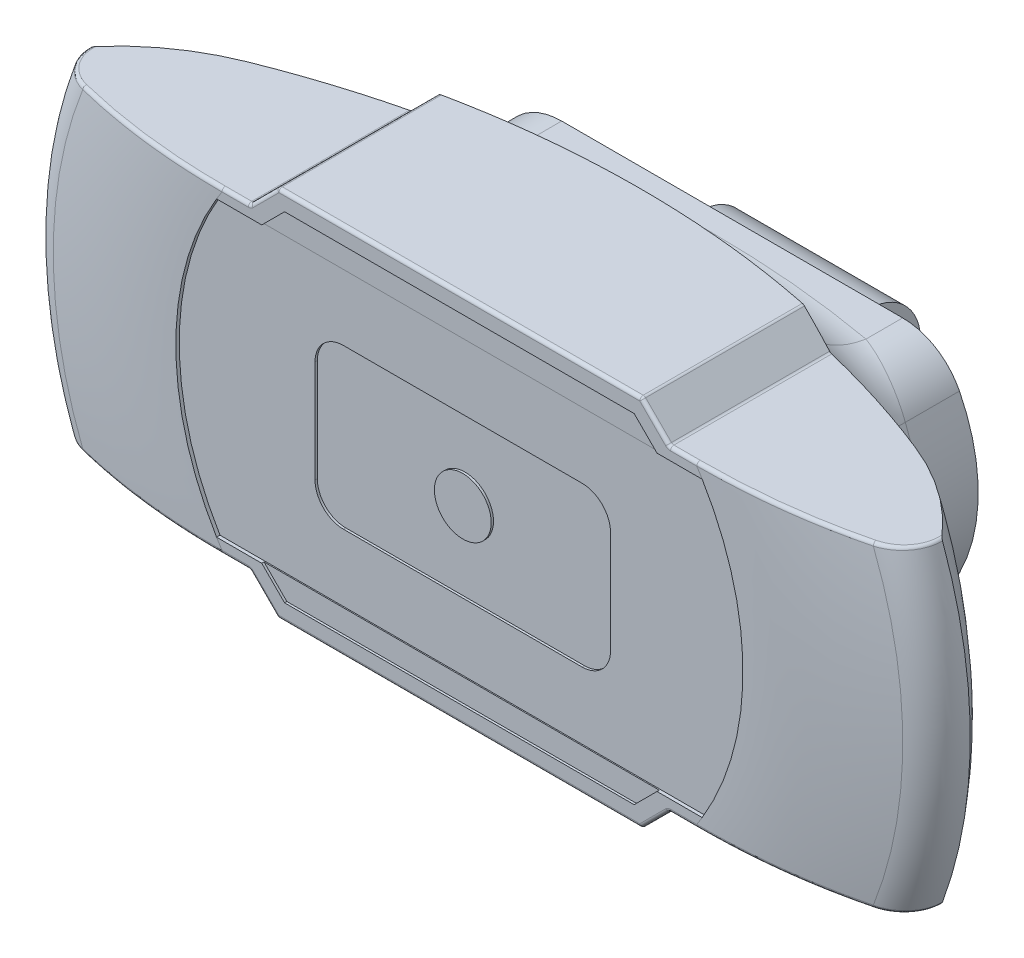
SolidWorks part; units mm, degrees
ref_plane "Front Plane" through (0, 0, 0) normal (0, 0, 1) x (1, 0, 0)
ref_plane "Top Plane" through (0, 0, 0) normal (0, 1, 0) x (1, 0, 0)
ref_plane "Right Plane" through (0, 0, 0) normal (1, 0, 0) x (0, 0, -1)
sketch "Sketch1" plane through (0, 0, 0) normal (0, 0, 1) x (1, 0, 0)
  line L0 (0, 16.4) -> (0, -16.4)
  line L1 (0, 16.4) -> (16, 16.4)
  line L2 (16, 16.4) -> (18.45, 13.95)
  line L3 (18.45, 13.95) -> (37.4353, 13.95)
  line L4 (0, -16.4) -> (16, -16.4)
  line L5 (16, -16.4) -> (18.45, -13.95)
  line L6 (18.45, -13.95) -> (37.4353, -13.95)
  line L7 (18.45, 13.95) -> (18.45, -13.95) construction
  line L8 (16, 16.4) -> (16, -16.4) construction
  arc A0 (37.4353, -13.95) -> (37.4353, 13.95) centre (0, 0) ccw
  dimension "D1" = 39.95
  dimension "D2" = 32.8
  dimension "D3" = 27.9
  dimension "D4" = 16
sketch "Sketch2" plane through (0, 0, 0) normal (0, 1, 0) x (1, 0, 0)
  line L0 (0, 0) -> (0, 17.6)
  line L1 (0, 17.6) -> (-9.2916, 17.6) construction
  line L2 (18.45, 0) -> (37.4353, 0) construction
  line L3 (39.95, 5) -> (39.95, 0) construction
  line L5 (24.95, 0) -> (0, 0)
  line L7 (0, 0) -> (39.95, 0) construction
  line L8 (37.4353, 0) -> (39.95, 0) construction
  line L9 (24.95, 0) -> (39.95, 5) construction
  arc A0 (0, 17.6) -> (32.5528, 10.7251) centre (0, -62.9071) cw
  arc A1 (32.5528, 10.7251) -> (39.95, 5) centre (24.6742, -7.0958) cw
  arc A3 (24.95, 0) -> (37.3743, 1.6406) centre (24.95, 47.8661) ccw
  arc A4 (37.3743, 1.6406) -> (39.95, 5) centre (36.4713, 5) ccw
  dimension "D1" = 17.6
  dimension "D2" = 15
  dimension "D3" = 5
revolve "Revolve1" add sketch "Sketch2" angle 180 mid plane about L0
sketch "Sketch3" plane through (0, 0, 0) normal (0, 0, 1) x (1, 0, 0)
  line L0 (0, 16.4) -> (0, -16.4) construction
  line L1 (0, -16.4) -> (16, -16.4) construction
  line L2 (16, -16.4) -> (18.45, -13.95) construction
  line L3 (18.45, -13.95) -> (37.4353, -13.95) construction
  line L4 (18.45, 13.95) -> (37.4353, 13.95) construction
  line L5 (16, 16.4) -> (18.45, 13.95) construction
  line L6 (0, 16.4) -> (16, 16.4) construction
  line L7 (0, 16.4) -> (0, -16.4)
  line L8 (0, -16.4) -> (16, -16.4)
  line L9 (16, -16.4) -> (18.45, -13.95)
  line L10 (18.45, -13.95) -> (37.4353, -13.95)
  line L11 (18.45, 13.95) -> (37.4353, 13.95)
  line L12 (16, 16.4) -> (18.45, 13.95)
  line L13 (0, 16.4) -> (16, 16.4)
  line L14 (-30, 46.4) -> (28.4264, 46.4)
  line L15 (28.4264, 46.4) -> (30.8764, 43.95)
  line L16 (30.8764, 43.95) -> (54.4187, 43.95)
  line L17 (30.8764, -43.95) -> (54.4187, -43.95)
  line L18 (28.4264, -46.4) -> (30.8764, -43.95)
  line L19 (-30, -46.4) -> (28.4264, -46.4)
  line L20 (-30, 46.4) -> (-30, -46.4)
  arc A0 (37.4353, -13.95) -> (37.4353, 13.95) centre (0, 0) ccw construction
  arc A1 (37.4353, -13.95) -> (37.4353, 13.95) centre (0, 0) ccw
  arc A2 (54.4187, -43.95) -> (54.4187, 43.95) centre (0, 0) ccw
  dimension "D1" = 30
extrude "Cut-Extrude1" cut sketch "Sketch3" against normal through all
mirror "Mirror1"
ref_plane "Plane1" through (0, 0, -24) normal (0, 0, 1) x (1, 0, 0)
sketch "Sketch4" plane through (0, 0, -24) normal (0, 0, 1) x (1, 0, 0)
  line L0 (0, 10) -> (0, -10) construction
  line L1 (-21.65, 0) -> (21.65, 0) construction
  line L2 (0, -10.6658) -> (0, 10.6658) construction
  line L3 (15, -10) -> (-15, -10)
  line L4 (15, -10) -> (15, 10) construction
  line L5 (15, 10) -> (-15, 10)
  line L6 (-15, -10) -> (-15, 10) construction
  line L7 (15, -10) -> (-15, 10) construction
  line L8 (15, 10) -> (-15, -10) construction
  line L9 (20, 6.9243) -> (20, -6.9243) construction
  arc A0 (20, 6.9243) -> (20, -6.9243) centre (6.2957, 0) cw
  arc A1 (15, 10) -> (20, 6.9243) centre (15, 4.398) cw
  arc A2 (15, -10) -> (20, -6.9243) centre (15, -4.398) ccw
  arc A3 (-15, -10) -> (-20, -6.9243) centre (-15, -4.398) cw
  arc A4 (-20, 6.9243) -> (-20, -6.9243) centre (-6.2957, 0) ccw
  arc A5 (-15, 10) -> (-20, 6.9243) centre (-15, 4.398) ccw
  point P4 (0, 0)
  dimension "D1" = 43.3
  dimension "D2" = 20
  dimension "D3" = 30
  dimension "D5" = 5
extrude "Boss-Extrude1" add sketch "Sketch4" along normal up to next
fillet "Fillet1" radius 6 8 edges at (-17.372, -9.4731, -15.1305) (-21.5174, 2.0133, -14.6451) (-18.5318, 8.7464, -14.9483) (0, 10, -16.9765) (17.372, 9.4731, -15.1305) (21.5174, -2.0133, -14.6451) (18.5318, -8.7464, -14.9483) (0, -10, -16.9765)
surface "Surface-Offset1" parameters "D1"=0.2
sketch "Sketch6" plane through (0, 0, 0) normal (0, 0, 1) x (1, 0, 0)
  line L21 (-17.3893, 12.8893) -> (-21.3628, 12.8893)
  line L23 (-24.95, 0) -> (0, 0)
  line L24 (-15.3787, 14.9) -> (-17.3893, 12.8893)
  line L25 (15.3787, 14.9) -> (-15.3787, 14.9)
  line L26 (17.3893, 12.8893) -> (15.3787, 14.9)
  line L27 (-15.3787, 14.9) -> (-17.3893, 12.8893)
  line L28 (15.3787, 14.9) -> (-15.3787, 14.9)
  line L29 (17.3893, 12.8893) -> (15.3787, 14.9)
  line L30 (0, 0) -> (24.95, 0)
  line L32 (21.3628, 12.8893) -> (17.3893, 12.8893)
  arc A2 (20.6857, -13.95) -> (20.6857, 13.95) centre (0, 0) ccw construction
  arc A3 (-20.6857, 13.95) -> (-20.6857, -13.95) centre (0, 0) ccw construction
  arc A4 (24.95, 0) -> (21.3628, 12.8893) centre (0, 0) ccw
  arc A5 (-21.3628, 12.8893) -> (-24.95, 0) centre (0, 0) ccw
  dimension "D1" = 1.5
extrude "Cut-Extrude6" cut sketch "Sketch6" against normal blind 0.3
mirror "Mirror2" of "Cut-Extrude6"
sketch "Sketch5" plane through (0, 0, -0.2) normal (0, 0, 1) x (1, 0, 0)
  line L1 (13, -7) -> (-13, -7)
  line L2 (13, -7) -> (13, 7)
  line L3 (13, 7) -> (-13, 7)
  line L4 (-13, -7) -> (-13, 7)
  line L5 (13, -7) -> (-13, 7) construction
  line L6 (13, 7) -> (-13, -7) construction
  circle A0 centre (0, 0) radius 2.5
  point P0 (0, 0)
  dimension "D3" = 5
  dimension "D1" = 26
  dimension "D2" = 14
extrude "Cut-Extrude2" cut sketch "Sketch5" against normal blind 0.3
fillet "Fillet2" radius 2.5 4 edges at (-13, 7, -0.4) (-13, -7, -0.4) (13, -7, -0.4) (13, 7, -0.4)
fillet "Fillet4" radius 0.3 8 edges at (18.45, 13.95, -7.1029) (16, -16.4, -7.1354) (18.45, -13.95, -7.1029) (16, 16.4, -7.1354) (-18.45, -13.95, -7.1029) (-16, -16.4, -7.1354) (-18.45, 13.95, -7.1029) (-16, 16.4, -7.1354)
fillet "Fillet5" radius 0.3 28 edges at (-19.63, -13.95, 0) (-17.225, -15.175, 0) (0, -16.4, 0) (17.225, -15.175, 0) (19.63, -13.95, 0) (15.9905, -16.3772, 0) (-15.9905, -16.3772, 0) (17.225, 15.175, 0) (0, 16.4, 0) (-17.225, 15.175, 0) (-15.9905, 16.3772, 0) (15.9905, 16.3772, 0) (-18.4595, -13.9728, 0) (18.4595, -13.9728, 0) (18.4595, 13.9728, 0) (-18.4595, 13.9728, 0) (19.63, 13.95, 0) (34.5934, 13.95, -7.7448) (36.5769, 13.95, -2.7767) (36.3384, -13.95, -2.5332) (-34.5934, 13.95, -7.7448) (-36.5769, 13.95, -2.7767) (-36.3384, -13.95, -2.5332) (-19.63, 13.95, 0)
sketch "Sketch8" plane through (0, 0, 0) normal (1, 0, 0) x (0, 0, -1)
  line L0 (24, -6.9243) -> (24, 6.9243) construction
  line L1 (24, 4.625) -> (28.5, 4.625)
  line L2 (24, 4.625) -> (24, -4.625)
  line L3 (24, -4.625) -> (28.5, -4.625)
  line L4 (28.5, 4.625) -> (28.5, -4.625) construction
  line L5 (0, 0) -> (24, 0) construction
  arc A0 (28.5, 4.625) -> (28.5, -4.625) centre (28.5, 0) cw
  circle A1 centre (28.5, 0) radius 2
  dimension "D3" = 4
  dimension "D1" = 28.5
  dimension "D2" = 9.25
extrude "Boss-Extrude2" add sketch "Sketch8" along normal mid plane 14.9
sketch "Sketch9" plane through (0, 0, -0.3) normal (0, 0, 1) x (1, 0, 0)
  line L0 (-15.3787, 14.9) -> (15.3787, 14.9)
  line L1 (15.3787, 14.9) -> (17.3893, 12.8893)
  line L2 (17.3893, 12.8893) -> (-17.3893, 12.8893)
  line L3 (-17.3893, 12.8893) -> (-15.3787, 14.9)
  line L4 (-17.3893, -12.8893) -> (-15.3787, -14.9)
  line L5 (-15.3787, -14.9) -> (-17.3893, -12.8893) construction
  line L6 (-15.3787, -14.9) -> (-17.3893, -12.8893) construction
  line L7 (-15.3787, -14.9) -> (15.3787, -14.9)
  line L8 (15.3787, -14.9) -> (17.3893, -12.8893)
  line L9 (17.3893, -12.8893) -> (15.3787, -14.9) construction
  line L10 (17.3893, -12.8893) -> (15.3787, -14.9) construction
  line L11 (17.3893, -12.8893) -> (-17.3893, -12.8893)
  line L12 (-17.3893, -12.8893) -> (-21.3628, -12.8893) construction
  point P15 (-17.3893, -12.8962)
extrude "Boss-Extrude3" add sketch "Sketch9" along normal blind 0.1
